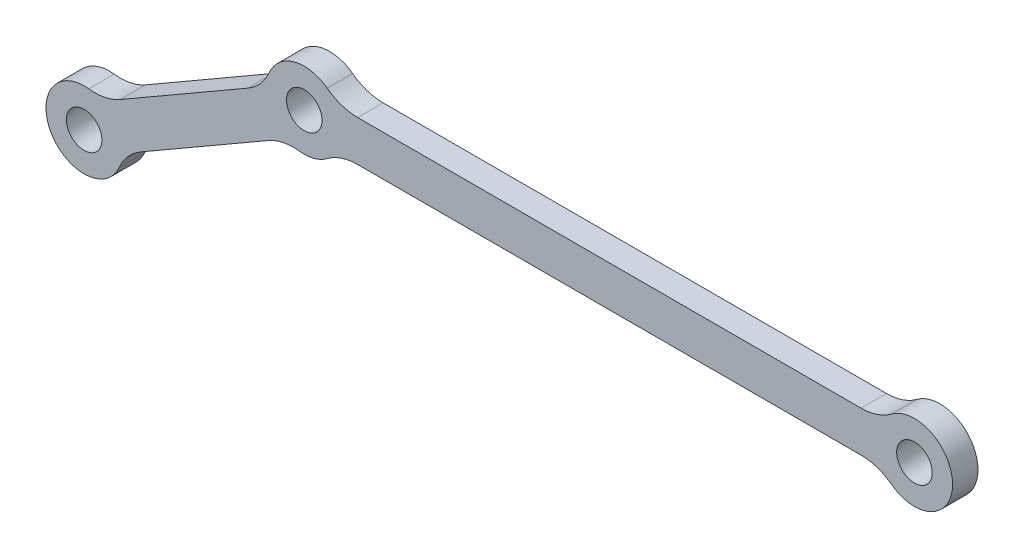
SolidWorks part; units mm, degrees
note: The reader was unsure of these and kept them because the rebuilt part matched: thickness of "Base-Flange1", "Sheet-Metal1".
ref_plane "Front Plane" through (0, 0, 0) normal (0, 0, 1) x (1, 0, 0)
ref_plane "Top Plane" through (0, 0, 0) normal (0, 1, 0) x (1, 0, 0)
ref_plane "Right Plane" through (0, 0, 0) normal (1, 0, 0) x (0, 0, -1)
sketch "Sketch1" plane through (0, 0, 0) normal (0, 0, 1) x (1, 0, 0)
  line L0 (-155.807, -25.292) -> (-123.4943, -6.6362)
  line L1 (-120, 0) -> (0, 0) construction
  line L3 (-113.6557, 4) -> (-6.3443, 4)
  line L5 (-113.6557, -4) -> (-6.3443, -4)
  line L6 (-60, 4) -> (-60, 0) construction
  line L7 (-60, 0) -> (-60, -4) construction
  line L8 (-127.4943, 0.292) -> (-159.807, -18.3638)
  line L9 (-120, 0) -> (-163.3013, -25) construction
  line L10 (-127.4943, 0.292) -> (-123.4943, -6.6362) construction
  line L11 (-159.807, -18.3638) -> (-155.807, -25.292) construction
  circle A0 centre (0, 0) radius 3.5
  arc A1 (-6.3443, -4) -> (-6.3443, 4) centre (0, 0) ccw
  circle A2 centre (-120, 0) radius 3.5
  circle A4 centre (-163.3013, -25) radius 3.5
  arc A6 (-127.4943, 0.292) -> (-113.6557, 4) centre (-120, 0) cw
  arc A7 (-159.807, -18.3638) -> (-155.807, -25.292) centre (-163.3013, -25) ccw
  arc A8 (-123.4943, -6.6362) -> (-113.6557, -4) centre (-120, 0) ccw
  arc A11 (-113.6557, -4) -> (-112.5, 0) centre (-120, 0) ccw construction
  arc A12 (-112.5, 0) -> (-113.6557, 4) centre (-120, 0) ccw construction
  arc A13 (-7.5, 0) -> (-6.3443, -4) centre (0, 0) ccw construction
  arc A14 (-6.3443, 4) -> (-7.5, 0) centre (0, 0) ccw construction
  point P3 (-157.807, -21.8279)
  dimension "D3" = 7
  dimension "D4" = 15
  dimension "D1" = 120
  dimension "D2" = 50
  dimension "D5" = 8
  dimension "D6" = 8
  dimension "D7" = 150
base flange "Base-Flange1" sketch "Sketch1" thickness 5 reverse thickness direction no parameters "D1"=0.7366
fillet "Fillet1" radius 10 8 edges at (-123.4943, -6.6362, -2.5) (-113.6557, -4, -2.5) (-155.807, -25.292, -2.5) (-159.807, -18.3638, -2.5) (-127.4943, 0.292, -2.5) (-113.6557, 4, -2.5) (-6.3443, -4, -2.5) (-6.3443, 4, -2.5)
sketch "Bend-Lines1" [suppressed] plane through (0, 0, 0) normal (0, 1, 0) x (1, 0, 0)
sketch "Bounding-Box1" [suppressed] plane through (0, 0, 0) normal (0, 1, 0) x (1, 0, 0)
sheet metal parameters "Sheet-Metal1" thickness 5 parameters "D1"=0.7366
flat pattern "Flat-Pattern1" [suppressed]
sketch "Bend-Lines2" plane through (0, 0, 0) normal (0, 1, 0) x (1, 0, 0)
sketch3d "Bounding-Box2" [suppressed]
  line L0 (-6.694, -8.2273, 0) -> (154.208, 8.3059, 0) construction
  line L1 (-9.481, 18.8957, 0) -> (151.421, 35.4289, 0) construction
  line L2 (-6.694, -8.2273, 0) -> (-9.481, 18.8957, 0) construction
  line L3 (154.208, 8.3059, 0) -> (151.421, 35.4289, 0) construction
